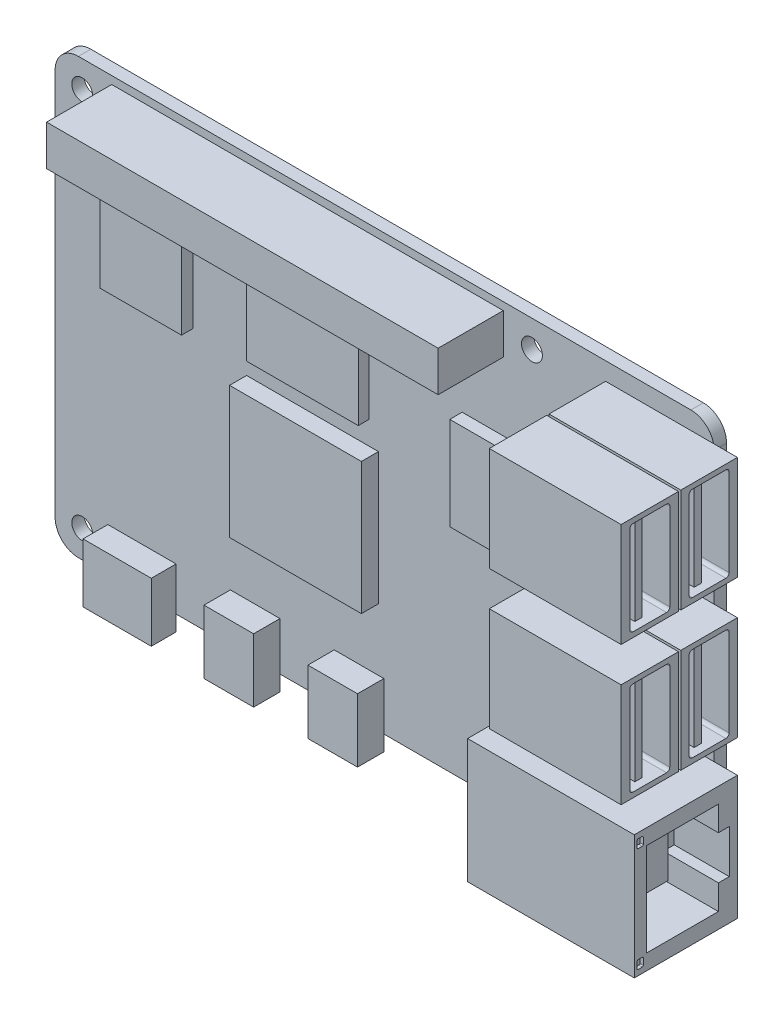
SolidWorks part; units mm, degrees
ref_plane "前视基准面" through (0, 0, 0) normal (0, 0, 1) x (1, 0, 0)
ref_plane "上视基准面" through (0, 0, 0) normal (0, 1, 0) x (1, 0, 0)
ref_plane "右视基准面" through (0, 0, 0) normal (1, 0, 0) x (0, 0, -1)
other "Configuration Table"
sketch "PCB_85x56_R3_MountPattern" plane through (0, 0, 0) normal (0, 0, 1) x (1, 0, 0)
  line L0 (-39.5, -28) -> (39.5, -28)
  line L1 (42.5, -25) -> (42.5, 25)
  line L2 (39.5, 28) -> (-39.5, 28)
  line L3 (-42.5, 25) -> (-42.5, -25)
  arc A0 (39.5, -28) -> (42.5, -25) centre (39.5, -25) ccw
  arc A1 (42.5, 25) -> (39.5, 28) centre (39.5, 25) ccw
  arc A2 (-39.5, 28) -> (-42.5, 25) centre (-39.5, 25) ccw
  arc A3 (-42.5, -25) -> (-39.5, -28) centre (-39.5, -25) ccw
  circle A4 centre (-39, -24.5) radius 1.35
  circle A5 centre (-39, 24.5) radius 1.35
  circle A6 centre (19, -24.5) radius 1.35
  circle A7 centre (19, 24.5) radius 1.35
extrude "PCB_Laminate_1p6" add sketch "PCB_85x56_R3_MountPattern" along normal blind 1.6 from offset 5.5 separate body
sketch "USB_C_Profile" plane through (0, 0, 0) normal (0, 0, 1) x (1, 0, 0)
  line L0 (-35.7, -30) -> (-26.9, -30)
  line L1 (-26.9, -30) -> (-26.9, -22.4)
  line L2 (-26.9, -22.4) -> (-35.7, -22.4)
  line L3 (-35.7, -22.4) -> (-35.7, -30)
extrude "USB_C" add sketch "USB_C_Profile" along normal blind 3.2 from offset 7.1 separate body
sketch "Micro_HDMI_1_Profile" plane through (0, 0, 0) normal (0, 0, 1) x (1, 0, 0)
  line L0 (-19.9, -30) -> (-13.5, -30)
  line L1 (-13.5, -30) -> (-13.5, -21.8)
  line L2 (-13.5, -21.8) -> (-19.9, -21.8)
  line L3 (-19.9, -21.8) -> (-19.9, -30)
extrude "Micro_HDMI_1" add sketch "Micro_HDMI_1_Profile" along normal blind 3.4 from offset 7.1 separate body
sketch "Micro_HDMI_2_Profile" plane through (0, 0, 0) normal (0, 0, 1) x (1, 0, 0)
  line L0 (-6.5, -30) -> (-0.1, -30)
  line L1 (-0.1, -30) -> (-0.1, -21.8)
  line L2 (-0.1, -21.8) -> (-6.5, -21.8)
  line L3 (-6.5, -21.8) -> (-6.5, -30)
extrude "Micro_HDMI_2" add sketch "Micro_HDMI_2_Profile" along normal blind 3.4 from offset 7.1 separate body
sketch "RJ45_Profile" plane through (0, 0, 0) normal (0, 0, 1) x (1, 0, 0)
  line L0 (24, -25.8) -> (45.5, -25.8)
  line L1 (45.5, -25.8) -> (45.5, -9.8)
  line L2 (45.5, -9.8) -> (24, -9.8)
  line L3 (24, -9.8) -> (24, -25.8)
extrude "RJ45" add sketch "RJ45_Profile" along normal blind 13.3 from offset 7.1 separate body
sketch "USB_A_1_Profile" plane through (0, 0, 0) normal (0, 0, 1) x (1, 0, 0)
  line L0 (28.5, -5.6) -> (45.5, -5.6)
  line L1 (45.5, -5.6) -> (45.5, 7.8)
  line L2 (45.5, 7.8) -> (28.5, 7.8)
  line L3 (28.5, 7.8) -> (28.5, -5.6)
extrude "USB_A_1" add sketch "USB_A_1_Profile" along normal blind 7.3 from offset 7.1 separate body
sketch "USB_A_2_Profile" plane through (0, 0, 0) normal (0, 0, 1) x (1, 0, 0)
  line L0 (28.5, -5.6) -> (45.5, -5.6)
  line L1 (45.5, -5.6) -> (45.5, 7.8)
  line L2 (45.5, 7.8) -> (28.5, 7.8)
  line L3 (28.5, 7.8) -> (28.5, -5.6)
extrude "USB_A_2" add sketch "USB_A_2_Profile" along normal blind 7.4 from offset 14.7 separate body
sketch "USB_A_3_Profile" plane through (0, 0, 0) normal (0, 0, 1) x (1, 0, 0)
  line L0 (28.5, 12.3) -> (45.5, 12.3)
  line L1 (45.5, 12.3) -> (45.5, 25.7)
  line L2 (45.5, 25.7) -> (28.5, 25.7)
  line L3 (28.5, 25.7) -> (28.5, 12.3)
extrude "USB_A_3" add sketch "USB_A_3_Profile" along normal blind 7.3 from offset 7.1 separate body
sketch "USB_A_4_Profile" plane through (0, 0, 0) normal (0, 0, 1) x (1, 0, 0)
  line L0 (28.5, 12.3) -> (45.5, 12.3)
  line L1 (45.5, 12.3) -> (45.5, 25.7)
  line L2 (45.5, 25.7) -> (28.5, 25.7)
  line L3 (28.5, 25.7) -> (28.5, 12.3)
extrude "USB_A_4" add sketch "USB_A_4_Profile" along normal blind 7.4 from offset 14.7 separate body
sketch "BCM2712_Profile" plane through (0, 0, 0) normal (0, 0, 1) x (1, 0, 0)
  line L0 (-17.8, -13.8) -> (-0.8, -13.8)
  line L1 (-0.8, -13.8) -> (-0.8, 3.2)
  line L2 (-0.8, 3.2) -> (-17.8, 3.2)
  line L3 (-17.8, 3.2) -> (-17.8, -13.8)
extrude "BCM2712" add sketch "BCM2712_Profile" along normal blind 2.2 from offset 7.1 separate body
sketch "RAM_Profile" plane through (0, 0, 0) normal (0, 0, 1) x (1, 0, 0)
  line L0 (-16.4, 6.2) -> (-2, 6.2)
  line L1 (-2, 6.2) -> (-2, 16.3)
  line L2 (-2, 16.3) -> (-16.4, 16.3)
  line L3 (-16.4, 16.3) -> (-16.4, 6.2)
extrude "RAM" add sketch "RAM_Profile" along normal blind 1.4 from offset 7.1 separate body
sketch "RP1_Profile" plane through (0, 0, 0) normal (0, 0, 1) x (1, 0, 0)
  line L0 (10, 1) -> (22, 1)
  line L1 (22, 1) -> (22, 13)
  line L2 (22, 13) -> (10, 13)
  line L3 (10, 13) -> (10, 1)
extrude "RP1" add sketch "RP1_Profile" along normal blind 1.6 from offset 7.1 separate body
sketch "Power_IC_Profile" plane through (0, 0, 0) normal (0, 0, 1) x (1, 0, 0)
  line L0 (-35.2, 5) -> (-24.7, 5)
  line L1 (-24.7, 5) -> (-24.7, 18)
  line L2 (-24.7, 18) -> (-35.2, 18)
  line L3 (-35.2, 18) -> (-35.2, 5)
extrude "Power_IC" add sketch "Power_IC_Profile" along normal blind 1.5 from offset 7.1 separate body
sketch "GPIO_Header_Profile" plane through (0, 0, 0) normal (0, 0, 1) x (1, 0, 0)
  line L0 (-35.2, 21.8) -> (15.3, 21.8)
  line L1 (15.3, 21.8) -> (15.3, 27)
  line L2 (15.3, 27) -> (-35.2, 27)
  line L3 (-35.2, 27) -> (-35.2, 21.8)
extrude "GPIO_Header" add sketch "GPIO_Header_Profile" along normal blind 8.4 from offset 7.1 separate body
sketch "Detail_USB_C_Receptacle_Profile" plane through (0, 0, 0) normal (0, 1, 0) x (1, 0, 0)
  line L0 (-34.04, -9.88) -> (-28.56, -9.88)
  line L1 (-27.42, -8.74) -> (-27.42, -8.66)
  line L2 (-28.56, -7.52) -> (-34.04, -7.52)
  line L3 (-35.18, -8.66) -> (-35.18, -8.74)
  arc A0 (-28.56, -9.88) -> (-27.42, -8.74) centre (-28.56, -8.74) ccw
  arc A1 (-27.42, -8.66) -> (-28.56, -7.52) centre (-28.56, -8.66) ccw
  arc A2 (-34.04, -7.52) -> (-35.18, -8.66) centre (-34.04, -8.66) ccw
  arc A3 (-35.18, -8.74) -> (-34.04, -9.88) centre (-34.04, -8.74) ccw
extrude "Detail_USB_C_Receptacle" cut sketch "Detail_USB_C_Receptacle_Profile" along normal blind 4.45 from offset 30.08 offset against normal yes
sketch "Detail_Micro_HDMI_Keyed_Receptacles_Profile" plane through (0, 0, 0) normal (0, 1, 0) x (1, 0, 0)
  line L0 (-19.45, -9.95) -> (-13.95, -9.95)
  line L1 (-13.95, -9.95) -> (-13.95, -8.48)
  line L2 (-13.95, -8.48) -> (-14.58, -7.65)
  line L3 (-14.58, -7.65) -> (-18.82, -7.65)
  line L4 (-18.82, -7.65) -> (-19.45, -8.48)
  line L5 (-19.45, -8.48) -> (-19.45, -9.95)
  line L6 (-6.05, -9.95) -> (-0.55, -9.95)
  line L7 (-0.55, -9.95) -> (-0.55, -8.48)
  line L8 (-0.55, -8.48) -> (-1.18, -7.65)
  line L9 (-1.18, -7.65) -> (-5.42, -7.65)
  line L10 (-5.42, -7.65) -> (-6.05, -8.48)
  line L11 (-6.05, -8.48) -> (-6.05, -9.95)
extrude "Detail_Micro_HDMI_Keyed_Receptacles" cut sketch "Detail_Micro_HDMI_Keyed_Receptacles_Profile" along normal blind 4.35 from offset 30.08 offset against normal yes
sketch "Detail_USB_A_Four_Receptacles_Profile" plane through (0, 0, 0) normal (1, 0, 0) x (0, 0, -1)
  line L0 (-12.91, -4.95) -> (-8.59, -4.95)
  line L1 (-8.17, -4.53) -> (-8.17, 6.73)
  line L2 (-8.59, 7.15) -> (-12.91, 7.15)
  line L3 (-13.33, 6.73) -> (-13.33, -4.53)
  line L4 (-20.56, -4.95) -> (-16.24, -4.95)
  line L5 (-15.82, -4.53) -> (-15.82, 6.73)
  line L6 (-16.24, 7.15) -> (-20.56, 7.15)
  line L7 (-20.98, 6.73) -> (-20.98, -4.53)
  line L8 (-12.91, 12.95) -> (-8.59, 12.95)
  line L9 (-8.17, 13.37) -> (-8.17, 24.63)
  line L10 (-8.59, 25.05) -> (-12.91, 25.05)
  line L11 (-13.33, 24.63) -> (-13.33, 13.37)
  line L12 (-20.56, 12.95) -> (-16.24, 12.95)
  line L13 (-15.82, 13.37) -> (-15.82, 24.63)
  line L14 (-16.24, 25.05) -> (-20.56, 25.05)
  line L15 (-20.98, 24.63) -> (-20.98, 13.37)
  arc A0 (-8.59, -4.95) -> (-8.17, -4.53) centre (-8.59, -4.53) ccw
  arc A1 (-8.17, 6.73) -> (-8.59, 7.15) centre (-8.59, 6.73) ccw
  arc A2 (-12.91, 7.15) -> (-13.33, 6.73) centre (-12.91, 6.73) ccw
  arc A3 (-13.33, -4.53) -> (-12.91, -4.95) centre (-12.91, -4.53) ccw
  arc A4 (-16.24, -4.95) -> (-15.82, -4.53) centre (-16.24, -4.53) ccw
  arc A5 (-15.82, 6.73) -> (-16.24, 7.15) centre (-16.24, 6.73) ccw
  arc A6 (-20.56, 7.15) -> (-20.98, 6.73) centre (-20.56, 6.73) ccw
  arc A7 (-20.98, -4.53) -> (-20.56, -4.95) centre (-20.56, -4.53) ccw
  arc A8 (-8.59, 12.95) -> (-8.17, 13.37) centre (-8.59, 13.37) ccw
  arc A9 (-8.17, 24.63) -> (-8.59, 25.05) centre (-8.59, 24.63) ccw
  arc A10 (-12.91, 25.05) -> (-13.33, 24.63) centre (-12.91, 24.63) ccw
  arc A11 (-13.33, 13.37) -> (-12.91, 12.95) centre (-12.91, 13.37) ccw
  arc A12 (-16.24, 12.95) -> (-15.82, 13.37) centre (-16.24, 13.37) ccw
  arc A13 (-15.82, 24.63) -> (-16.24, 25.05) centre (-16.24, 24.63) ccw
  arc A14 (-20.56, 25.05) -> (-20.98, 24.63) centre (-20.56, 24.63) ccw
  arc A15 (-20.98, 13.37) -> (-20.56, 12.95) centre (-20.56, 13.37) ccw
extrude "Detail_USB_A_Four_Receptacles" cut sketch "Detail_USB_A_Four_Receptacles_Profile" against normal blind 6.28 from offset 45.58
sketch "Detail_RJ45_Keyed_Receptacle_Profile" plane through (0, 0, 0) normal (1, 0, 0) x (0, 0, -1)
  line L0 (-18.8, -23.8) -> (-18.8, -11.8)
  line L1 (-18.8, -11.8) -> (-9.55, -11.8)
  line L2 (-9.55, -11.8) -> (-9.55, -15)
  line L3 (-9.55, -15) -> (-8.15, -15)
  line L4 (-8.15, -15) -> (-8.15, -20.6)
  line L5 (-8.15, -20.6) -> (-9.55, -20.6)
  line L6 (-9.55, -20.6) -> (-9.55, -23.8)
  line L7 (-9.55, -23.8) -> (-18.8, -23.8)
extrude "Detail_RJ45_Keyed_Receptacle" cut sketch "Detail_RJ45_Keyed_Receptacle_Profile" against normal blind 7.18 from offset 45.58
sketch "Detail_RJ45_LED_Pockets_Profile" plane through (0, 0, 0) normal (1, 0, 0) x (0, 0, -1)
  line L0 (-19.9, -25.1) -> (-19.38, -25.1)
  line L1 (-19.24, -24.96) -> (-19.24, -24.14)
  line L2 (-19.38, -24) -> (-19.9, -24)
  line L3 (-20.04, -24.14) -> (-20.04, -24.96)
  line L4 (-19.9, -11.6) -> (-19.38, -11.6)
  line L5 (-19.24, -11.46) -> (-19.24, -10.64)
  line L6 (-19.38, -10.5) -> (-19.9, -10.5)
  line L7 (-20.04, -10.64) -> (-20.04, -11.46)
  arc A0 (-19.38, -25.1) -> (-19.24, -24.96) centre (-19.38, -24.96) ccw
  arc A1 (-19.24, -24.14) -> (-19.38, -24) centre (-19.38, -24.14) ccw
  arc A2 (-19.9, -24) -> (-20.04, -24.14) centre (-19.9, -24.14) ccw
  arc A3 (-20.04, -24.96) -> (-19.9, -25.1) centre (-19.9, -24.96) ccw
  arc A4 (-19.38, -11.6) -> (-19.24, -11.46) centre (-19.38, -11.46) ccw
  arc A5 (-19.24, -10.64) -> (-19.38, -10.5) centre (-19.38, -10.64) ccw
  arc A6 (-19.9, -10.5) -> (-20.04, -10.64) centre (-19.9, -10.64) ccw
  arc A7 (-20.04, -11.46) -> (-19.9, -11.6) centre (-19.9, -11.46) ccw
extrude "Detail_RJ45_LED_Pockets" cut sketch "Detail_RJ45_LED_Pockets_Profile" against normal blind 1.12 from offset 45.58
sketch "USB_C_Insulated_Tongue_Profile" plane through (0, 0, 0) normal (0, 0, 1) x (1, 0, 0)
  line L0 (-34.06, -29.37) -> (-28.54, -29.37)
  line L1 (-28.54, -29.37) -> (-28.54, -25.64)
  line L2 (-28.54, -25.64) -> (-34.06, -25.64)
  line L3 (-34.06, -25.64) -> (-34.06, -29.37)
extrude "USB_C_Insulated_Tongue" add sketch "USB_C_Insulated_Tongue_Profile" along normal blind 0.52 from offset 8.44 separate body
sketch "USB_C_Gold_Contact_Row_Profile" plane through (0, 0, 0) normal (0, 0, 1) x (1, 0, 0)
  line L0 (-33.485, -28.95) -> (-33.245, -28.95)
  line L1 (-33.245, -28.95) -> (-33.245, -27.24)
  line L2 (-33.245, -27.24) -> (-33.485, -27.24)
  line L3 (-33.485, -27.24) -> (-33.485, -28.95)
  line L4 (-32.895, -28.95) -> (-32.655, -28.95)
  line L5 (-32.655, -28.95) -> (-32.655, -27.24)
  line L6 (-32.655, -27.24) -> (-32.895, -27.24)
  line L7 (-32.895, -27.24) -> (-32.895, -28.95)
  line L8 (-32.305, -28.95) -> (-32.065, -28.95)
  line L9 (-32.065, -28.95) -> (-32.065, -27.24)
  line L10 (-32.065, -27.24) -> (-32.305, -27.24)
  line L11 (-32.305, -27.24) -> (-32.305, -28.95)
  line L12 (-31.715, -28.95) -> (-31.475, -28.95)
  line L13 (-31.475, -28.95) -> (-31.475, -27.24)
  line L14 (-31.475, -27.24) -> (-31.715, -27.24)
  line L15 (-31.715, -27.24) -> (-31.715, -28.95)
  line L16 (-31.125, -28.95) -> (-30.885, -28.95)
  line L17 (-30.885, -28.95) -> (-30.885, -27.24)
  line L18 (-30.885, -27.24) -> (-31.125, -27.24)
  line L19 (-31.125, -27.24) -> (-31.125, -28.95)
  line L20 (-30.535, -28.95) -> (-30.295, -28.95)
  line L21 (-30.295, -28.95) -> (-30.295, -27.24)
  line L22 (-30.295, -27.24) -> (-30.535, -27.24)
  line L23 (-30.535, -27.24) -> (-30.535, -28.95)
  line L24 (-29.945, -28.95) -> (-29.705, -28.95)
  line L25 (-29.705, -28.95) -> (-29.705, -27.24)
  line L26 (-29.705, -27.24) -> (-29.945, -27.24)
  line L27 (-29.945, -27.24) -> (-29.945, -28.95)
  line L28 (-29.355, -28.95) -> (-29.115, -28.95)
  line L29 (-29.115, -28.95) -> (-29.115, -27.24)
  line L30 (-29.115, -27.24) -> (-29.355, -27.24)
  line L31 (-29.355, -27.24) -> (-29.355, -28.95)
extrude "USB_C_Gold_Contact_Row" add sketch "USB_C_Gold_Contact_Row_Profile" along normal blind 0.08 from offset 8.96 separate body
sketch "Micro_HDMI_1_Tongue_Profile" plane through (0, 0, 0) normal (0, 0, 1) x (1, 0, 0)
  line L0 (-18.58, -29.18) -> (-14.82, -29.18)
  line L1 (-14.82, -29.18) -> (-14.82, -25.75)
  line L2 (-14.82, -25.75) -> (-18.58, -25.75)
  line L3 (-18.58, -25.75) -> (-18.58, -29.18)
extrude "Micro_HDMI_1_Tongue" add sketch "Micro_HDMI_1_Tongue_Profile" along normal blind 0.43 from offset 8.49 separate body
sketch "Micro_HDMI_2_Tongue_Profile" plane through (0, 0, 0) normal (0, 0, 1) x (1, 0, 0)
  line L0 (-5.18, -29.18) -> (-1.42, -29.18)
  line L1 (-1.42, -29.18) -> (-1.42, -25.75)
  line L2 (-1.42, -25.75) -> (-5.18, -25.75)
  line L3 (-5.18, -25.75) -> (-5.18, -29.18)
extrude "Micro_HDMI_2_Tongue" add sketch "Micro_HDMI_2_Tongue_Profile" along normal blind 0.43 from offset 8.49 separate body
sketch "Micro_HDMI_Gold_Contact_Rows_Profile" plane through (0, 0, 0) normal (0, 0, 1) x (1, 0, 0)
  line L0 (-18.205, -28.92) -> (-18.015, -28.92)
  line L1 (-18.015, -28.92) -> (-18.015, -27.25)
  line L2 (-18.015, -27.25) -> (-18.205, -27.25)
  line L3 (-18.205, -27.25) -> (-18.205, -28.92)
  line L4 (-17.735, -28.92) -> (-17.545, -28.92)
  line L5 (-17.545, -28.92) -> (-17.545, -27.25)
  line L6 (-17.545, -27.25) -> (-17.735, -27.25)
  line L7 (-17.735, -27.25) -> (-17.735, -28.92)
  line L8 (-17.265, -28.92) -> (-17.075, -28.92)
  line L9 (-17.075, -28.92) -> (-17.075, -27.25)
  line L10 (-17.075, -27.25) -> (-17.265, -27.25)
  line L11 (-17.265, -27.25) -> (-17.265, -28.92)
  line L12 (-16.795, -28.92) -> (-16.605, -28.92)
  line L13 (-16.605, -28.92) -> (-16.605, -27.25)
  line L14 (-16.605, -27.25) -> (-16.795, -27.25)
  line L15 (-16.795, -27.25) -> (-16.795, -28.92)
  line L16 (-16.325, -28.92) -> (-16.135, -28.92)
  line L17 (-16.135, -28.92) -> (-16.135, -27.25)
  line L18 (-16.135, -27.25) -> (-16.325, -27.25)
  line L19 (-16.325, -27.25) -> (-16.325, -28.92)
  line L20 (-15.855, -28.92) -> (-15.665, -28.92)
  line L21 (-15.665, -28.92) -> (-15.665, -27.25)
  line L22 (-15.665, -27.25) -> (-15.855, -27.25)
  line L23 (-15.855, -27.25) -> (-15.855, -28.92)
  line L24 (-15.385, -28.92) -> (-15.195, -28.92)
  line L25 (-15.195, -28.92) -> (-15.195, -27.25)
  line L26 (-15.195, -27.25) -> (-15.385, -27.25)
  line L27 (-15.385, -27.25) -> (-15.385, -28.92)
  line L28 (-4.805, -28.92) -> (-4.615, -28.92)
  line L29 (-4.615, -28.92) -> (-4.615, -27.25)
  line L30 (-4.615, -27.25) -> (-4.805, -27.25)
  line L31 (-4.805, -27.25) -> (-4.805, -28.92)
  line L32 (-4.335, -28.92) -> (-4.145, -28.92)
  line L33 (-4.145, -28.92) -> (-4.145, -27.25)
  line L34 (-4.145, -27.25) -> (-4.335, -27.25)
  line L35 (-4.335, -27.25) -> (-4.335, -28.92)
  line L36 (-3.865, -28.92) -> (-3.675, -28.92)
  line L37 (-3.675, -28.92) -> (-3.675, -27.25)
  line L38 (-3.675, -27.25) -> (-3.865, -27.25)
  line L39 (-3.865, -27.25) -> (-3.865, -28.92)
  line L40 (-3.395, -28.92) -> (-3.205, -28.92)
  line L41 (-3.205, -28.92) -> (-3.205, -27.25)
  line L42 (-3.205, -27.25) -> (-3.395, -27.25)
  line L43 (-3.395, -27.25) -> (-3.395, -28.92)
  line L44 (-2.925, -28.92) -> (-2.735, -28.92)
  line L45 (-2.735, -28.92) -> (-2.735, -27.25)
  line L46 (-2.735, -27.25) -> (-2.925, -27.25)
  line L47 (-2.925, -27.25) -> (-2.925, -28.92)
  line L48 (-2.455, -28.92) -> (-2.265, -28.92)
  line L49 (-2.265, -28.92) -> (-2.265, -27.25)
  line L50 (-2.265, -27.25) -> (-2.455, -27.25)
  line L51 (-2.455, -27.25) -> (-2.455, -28.92)
  line L52 (-1.985, -28.92) -> (-1.795, -28.92)
  line L53 (-1.795, -28.92) -> (-1.795, -27.25)
  line L54 (-1.795, -27.25) -> (-1.985, -27.25)
  line L55 (-1.985, -27.25) -> (-1.985, -28.92)
extrude "Micro_HDMI_Gold_Contact_Rows" add sketch "Micro_HDMI_Gold_Contact_Rows_Profile" along normal blind 0.065 from offset 8.92 separate body
sketch "USB_A_1_Insulated_Tongue_Profile" plane through (0, 0, 0) normal (0, 0, 1) x (1, 0, 0)
  line L0 (39.38, -4.52) -> (44.9, -4.52)
  line L1 (44.9, -4.52) -> (44.9, 6.72)
  line L2 (44.9, 6.72) -> (39.38, 6.72)
  line L3 (39.38, 6.72) -> (39.38, -4.52)
extrude "USB_A_1_Insulated_Tongue" add sketch "USB_A_1_Insulated_Tongue_Profile" along normal blind 0.92 from offset 11.16 separate body
sketch "USB_A_1_Gold_Contact_Row_Profile" plane through (0, 0, 0) normal (0, 0, 1) x (1, 0, 0)
  line L0 (42.3, -2.34) -> (44.5, -2.34)
  line L1 (44.5, -2.34) -> (44.5, -1.64)
  line L2 (44.5, -1.64) -> (42.3, -1.64)
  line L3 (42.3, -1.64) -> (42.3, -2.34)
  line L4 (42.3, -0.28) -> (44.5, -0.28)
  line L5 (44.5, -0.28) -> (44.5, 0.42)
  line L6 (44.5, 0.42) -> (42.3, 0.42)
  line L7 (42.3, 0.42) -> (42.3, -0.28)
  line L8 (42.3, 1.78) -> (44.5, 1.78)
  line L9 (44.5, 1.78) -> (44.5, 2.48)
  line L10 (44.5, 2.48) -> (42.3, 2.48)
  line L11 (42.3, 2.48) -> (42.3, 1.78)
  line L12 (42.3, 3.84) -> (44.5, 3.84)
  line L13 (44.5, 3.84) -> (44.5, 4.54)
  line L14 (44.5, 4.54) -> (42.3, 4.54)
  line L15 (42.3, 4.54) -> (42.3, 3.84)
extrude "USB_A_1_Gold_Contact_Row" add sketch "USB_A_1_Gold_Contact_Row_Profile" along normal blind 0.11 from offset 11.05 separate body
sketch "USB_A_2_Insulated_Tongue_Profile" plane through (0, 0, 0) normal (0, 0, 1) x (1, 0, 0)
  line L0 (39.38, -4.52) -> (44.9, -4.52)
  line L1 (44.9, -4.52) -> (44.9, 6.72)
  line L2 (44.9, 6.72) -> (39.38, 6.72)
  line L3 (39.38, 6.72) -> (39.38, -4.52)
extrude "USB_A_2_Insulated_Tongue" add sketch "USB_A_2_Insulated_Tongue_Profile" along normal blind 0.92 from offset 18.81 separate body
sketch "USB_A_2_Gold_Contact_Row_Profile" plane through (0, 0, 0) normal (0, 0, 1) x (1, 0, 0)
  line L0 (42.3, -2.34) -> (44.5, -2.34)
  line L1 (44.5, -2.34) -> (44.5, -1.64)
  line L2 (44.5, -1.64) -> (42.3, -1.64)
  line L3 (42.3, -1.64) -> (42.3, -2.34)
  line L4 (42.3, -0.28) -> (44.5, -0.28)
  line L5 (44.5, -0.28) -> (44.5, 0.42)
  line L6 (44.5, 0.42) -> (42.3, 0.42)
  line L7 (42.3, 0.42) -> (42.3, -0.28)
  line L8 (42.3, 1.78) -> (44.5, 1.78)
  line L9 (44.5, 1.78) -> (44.5, 2.48)
  line L10 (44.5, 2.48) -> (42.3, 2.48)
  line L11 (42.3, 2.48) -> (42.3, 1.78)
  line L12 (42.3, 3.84) -> (44.5, 3.84)
  line L13 (44.5, 3.84) -> (44.5, 4.54)
  line L14 (44.5, 4.54) -> (42.3, 4.54)
  line L15 (42.3, 4.54) -> (42.3, 3.84)
extrude "USB_A_2_Gold_Contact_Row" add sketch "USB_A_2_Gold_Contact_Row_Profile" along normal blind 0.11 from offset 18.7 separate body
sketch "USB_A_3_Insulated_Tongue_Profile" plane through (0, 0, 0) normal (0, 0, 1) x (1, 0, 0)
  line L0 (39.38, 13.38) -> (44.9, 13.38)
  line L1 (44.9, 13.38) -> (44.9, 24.62)
  line L2 (44.9, 24.62) -> (39.38, 24.62)
  line L3 (39.38, 24.62) -> (39.38, 13.38)
extrude "USB_A_3_Insulated_Tongue" add sketch "USB_A_3_Insulated_Tongue_Profile" along normal blind 0.92 from offset 11.16 separate body
sketch "USB_A_3_Gold_Contact_Row_Profile" plane through (0, 0, 0) normal (0, 0, 1) x (1, 0, 0)
  line L0 (42.3, 15.56) -> (44.5, 15.56)
  line L1 (44.5, 15.56) -> (44.5, 16.26)
  line L2 (44.5, 16.26) -> (42.3, 16.26)
  line L3 (42.3, 16.26) -> (42.3, 15.56)
  line L4 (42.3, 17.62) -> (44.5, 17.62)
  line L5 (44.5, 17.62) -> (44.5, 18.32)
  line L6 (44.5, 18.32) -> (42.3, 18.32)
  line L7 (42.3, 18.32) -> (42.3, 17.62)
  line L8 (42.3, 19.68) -> (44.5, 19.68)
  line L9 (44.5, 19.68) -> (44.5, 20.38)
  line L10 (44.5, 20.38) -> (42.3, 20.38)
  line L11 (42.3, 20.38) -> (42.3, 19.68)
  line L12 (42.3, 21.74) -> (44.5, 21.74)
  line L13 (44.5, 21.74) -> (44.5, 22.44)
  line L14 (44.5, 22.44) -> (42.3, 22.44)
  line L15 (42.3, 22.44) -> (42.3, 21.74)
extrude "USB_A_3_Gold_Contact_Row" add sketch "USB_A_3_Gold_Contact_Row_Profile" along normal blind 0.11 from offset 11.05 separate body
sketch "USB_A_4_Insulated_Tongue_Profile" plane through (0, 0, 0) normal (0, 0, 1) x (1, 0, 0)
  line L0 (39.38, 13.38) -> (44.9, 13.38)
  line L1 (44.9, 13.38) -> (44.9, 24.62)
  line L2 (44.9, 24.62) -> (39.38, 24.62)
  line L3 (39.38, 24.62) -> (39.38, 13.38)
extrude "USB_A_4_Insulated_Tongue" add sketch "USB_A_4_Insulated_Tongue_Profile" along normal blind 0.92 from offset 18.81 separate body
sketch "USB_A_4_Gold_Contact_Row_Profile" plane through (0, 0, 0) normal (0, 0, 1) x (1, 0, 0)
  line L0 (42.3, 15.56) -> (44.5, 15.56)
  line L1 (44.5, 15.56) -> (44.5, 16.26)
  line L2 (44.5, 16.26) -> (42.3, 16.26)
  line L3 (42.3, 16.26) -> (42.3, 15.56)
  line L4 (42.3, 17.62) -> (44.5, 17.62)
  line L5 (44.5, 17.62) -> (44.5, 18.32)
  line L6 (44.5, 18.32) -> (42.3, 18.32)
  line L7 (42.3, 18.32) -> (42.3, 17.62)
  line L8 (42.3, 19.68) -> (44.5, 19.68)
  line L9 (44.5, 19.68) -> (44.5, 20.38)
  line L10 (44.5, 20.38) -> (42.3, 20.38)
  line L11 (42.3, 20.38) -> (42.3, 19.68)
  line L12 (42.3, 21.74) -> (44.5, 21.74)
  line L13 (44.5, 21.74) -> (44.5, 22.44)
  line L14 (44.5, 22.44) -> (42.3, 22.44)
  line L15 (42.3, 22.44) -> (42.3, 21.74)
extrude "USB_A_4_Gold_Contact_Row" add sketch "USB_A_4_Gold_Contact_Row_Profile" along normal blind 0.11 from offset 18.7 separate body
sketch "RJ45_Dark_Backpiece_Profile" plane through (0, 0, 0) normal (0, 0, 1) x (1, 0, 0)
  line L0 (38.43, -23.55) -> (39.05, -23.55)
  line L1 (39.05, -23.55) -> (39.05, -12.05)
  line L2 (39.05, -12.05) -> (38.43, -12.05)
  line L3 (38.43, -12.05) -> (38.43, -23.55)
extrude "RJ45_Dark_Backpiece" add sketch "RJ45_Dark_Backpiece_Profile" along normal blind 9.06 from offset 9.62 separate body
sketch "RJ45_Contact_Carrier_Profile" plane through (0, 0, 0) normal (0, 0, 1) x (1, 0, 0)
  line L0 (39.05, -22.8) -> (43.98, -22.8)
  line L1 (43.98, -22.8) -> (43.98, -12.8)
  line L2 (43.98, -12.8) -> (39.05, -12.8)
  line L3 (39.05, -12.8) -> (39.05, -22.8)
extrude "RJ45_Contact_Carrier" add sketch "RJ45_Contact_Carrier_Profile" along normal blind 0.7 from offset 17.75 separate body
sketch "RJ45_Eight_Gold_Contacts_Profile" plane through (0, 0, 0) normal (0, 0, 1) x (1, 0, 0)
  line L0 (40.1, -21.35) -> (44.28, -21.35)
  line L1 (44.28, -21.35) -> (44.28, -21.04)
  line L2 (44.28, -21.04) -> (40.1, -21.04)
  line L3 (40.1, -21.04) -> (40.1, -21.35)
  line L4 (40.1, -20.38) -> (44.28, -20.38)
  line L5 (44.28, -20.38) -> (44.28, -20.07)
  line L6 (44.28, -20.07) -> (40.1, -20.07)
  line L7 (40.1, -20.07) -> (40.1, -20.38)
  line L8 (40.1, -19.41) -> (44.28, -19.41)
  line L9 (44.28, -19.41) -> (44.28, -19.1)
  line L10 (44.28, -19.1) -> (40.1, -19.1)
  line L11 (40.1, -19.1) -> (40.1, -19.41)
  line L12 (40.1, -18.44) -> (44.28, -18.44)
  line L13 (44.28, -18.44) -> (44.28, -18.13)
  line L14 (44.28, -18.13) -> (40.1, -18.13)
  line L15 (40.1, -18.13) -> (40.1, -18.44)
  line L16 (40.1, -17.47) -> (44.28, -17.47)
  line L17 (44.28, -17.47) -> (44.28, -17.16)
  line L18 (44.28, -17.16) -> (40.1, -17.16)
  line L19 (40.1, -17.16) -> (40.1, -17.47)
  line L20 (40.1, -16.5) -> (44.28, -16.5)
  line L21 (44.28, -16.5) -> (44.28, -16.19)
  line L22 (44.28, -16.19) -> (40.1, -16.19)
  line L23 (40.1, -16.19) -> (40.1, -16.5)
  line L24 (40.1, -15.53) -> (44.28, -15.53)
  line L25 (44.28, -15.53) -> (44.28, -15.22)
  line L26 (44.28, -15.22) -> (40.1, -15.22)
  line L27 (40.1, -15.22) -> (40.1, -15.53)
  line L28 (40.1, -14.56) -> (44.28, -14.56)
  line L29 (44.28, -14.56) -> (44.28, -14.25)
  line L30 (44.28, -14.25) -> (40.1, -14.25)
  line L31 (40.1, -14.25) -> (40.1, -14.56)
extrude "RJ45_Eight_Gold_Contacts" add sketch "RJ45_Eight_Gold_Contacts_Profile" along normal blind 0.15 from offset 17.6 separate body
sketch "RJ45_Green_Indicator_Profile" plane through (0, 0, 0) normal (0, 0, 1) x (1, 0, 0)
  line L0 (44.55, -24.98) -> (45.18, -24.98)
  line L1 (45.18, -24.98) -> (45.18, -24.12)
  line L2 (45.18, -24.12) -> (44.55, -24.12)
  line L3 (44.55, -24.12) -> (44.55, -24.98)
extrude "RJ45_Green_Indicator" add sketch "RJ45_Green_Indicator_Profile" along normal blind 0.54 from offset 19.37 separate body
sketch "RJ45_Amber_Indicator_Profile" plane through (0, 0, 0) normal (0, 0, 1) x (1, 0, 0)
  line L0 (44.55, -11.48) -> (45.18, -11.48)
  line L1 (45.18, -11.48) -> (45.18, -10.62)
  line L2 (45.18, -10.62) -> (44.55, -10.62)
  line L3 (44.55, -10.62) -> (44.55, -11.48)
extrude "RJ45_Amber_Indicator" add sketch "RJ45_Amber_Indicator_Profile" along normal blind 0.54 from offset 19.37 separate body
